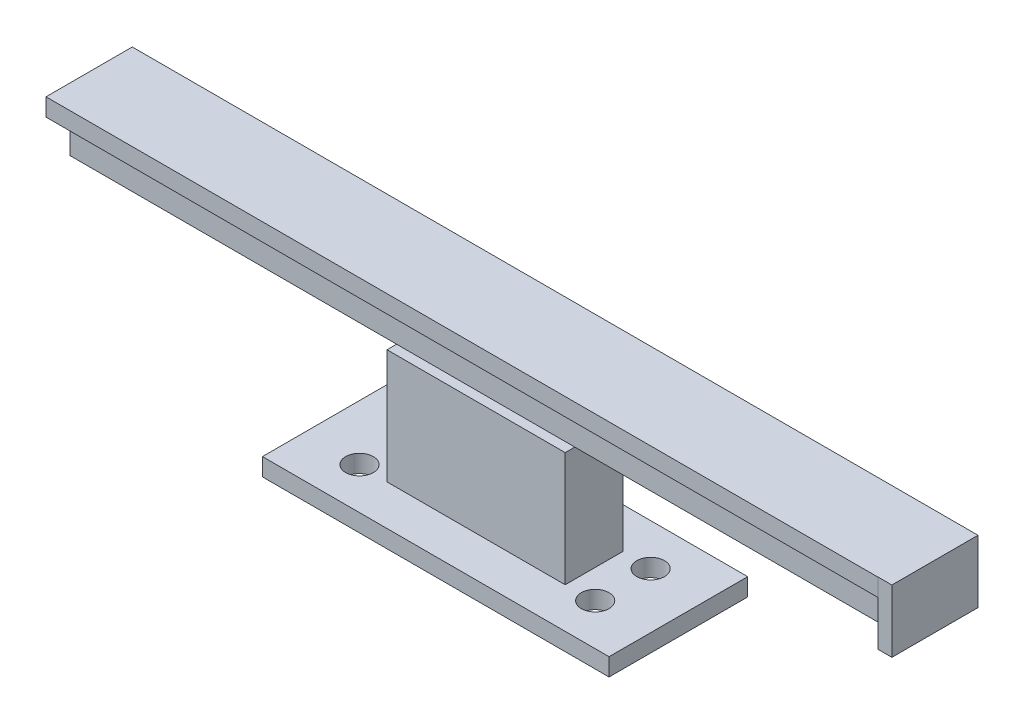
SolidWorks part; units mm, degrees
ref_plane "Front" through (0, 0, 0) normal (0, 0, 1) x (1, 0, 0)
ref_plane "Top" through (0, 0, 0) normal (0, 1, 0) x (1, 0, 0)
ref_plane "Right" through (0, 0, 0) normal (1, 0, 0) x (0, 0, -1)
sketch "Sketch1" plane through (0, 0, 0) normal (0, 1, 0) x (1, 0, 0)
  line L0 (0, 0) -> (0, -3.6978)
  line L1 (25, -12.5) -> (-25, -12.5)
  line L2 (25, -12.5) -> (25, 7.5)
  line L3 (25, 7.5) -> (-25, 7.5)
  line L4 (-25, -12.5) -> (-25, 7.5)
  circle A0 centre (17, -6.5) radius 2
  circle A1 centre (17, 1.5) radius 2
  circle A2 centre (-17, -6.5) radius 2
  circle A3 centre (-17, 1.5) radius 2
  point P0 (0, 0)
  dimension "D4" = 4
  dimension "D5" = 4
  dimension "D1" = 50
  dimension "D2" = 20
  dimension "D3" = 8
  dimension "D6" = 6
  dimension "D7" = 6
  dimension "D8" = 34
extrude "Boss-Extrude1" add sketch "Sketch1" along normal blind 2.54 contours L4 L1 L2 L3 A2 A1 A0 A3 region at (0, 0, 11.9615)
sketch "Sketch2" plane through (0, 2.54, 0) normal (0, 1, 0) x (1, 0, 0)
  line L1 (12.8489, -6.6773) -> (-12.8489, -6.6773)
  line L2 (12.8489, -6.6773) -> (12.8489, 1.6773)
  line L3 (12.8489, 1.6773) -> (-12.8489, 1.6773)
  line L4 (-12.8489, -6.6773) -> (-12.8489, 1.6773)
  line L5 (12.8489, -6.6773) -> (-12.8489, 1.6773) construction
  line L6 (12.8489, 1.6773) -> (-12.8489, -6.6773) construction
  point P0 (0, -2.5)
extrude "Boss-Extrude2" add sketch "Sketch2" along normal blind 16.51
sketch "Sketch3" plane through (0, 19.05, 0) normal (0, 1, 0) x (1, 0, 0)
  line L0 (-12.8489, -6.6773) -> (12.8489, -6.6773) construction
  line L1 (60, -5.294) -> (-60, -5.294)
  line L2 (60, -5.294) -> (60, 0.294)
  line L3 (60, 0.294) -> (-60, 0.294)
  line L4 (-60, -5.294) -> (-60, 0.294)
  line L5 (60, -5.294) -> (-60, 0.294) construction
  line L6 (60, 0.294) -> (-60, -5.294) construction
  line L7 (12.8489, -6.6773) -> (12.8489, 1.6773) construction
  point P0 (0, -2.5)
  point P5 (0, -2.5)
  dimension "D1" = 5.588
  dimension "D2" = 4.1773
  dimension "D3" = 0
  dimension "D4" = 12.8489
  dimension "D5" = 120
extrude "Boss-Extrude3" add sketch "Sketch3" along normal blind 6.51
sketch "Sketch4" plane through (0, 25.56, 0) normal (0, 1, 0) x (1, 0, 0)
  line L0 (60, 0.294) -> (-60, 0.294) construction
  line L1 (60, -8.723) -> (-60, -8.723)
  line L2 (60, -8.723) -> (60, 3.723)
  line L3 (60, 3.723) -> (-60, 3.723)
  line L4 (-60, -8.723) -> (-60, 3.723)
  line L5 (60, -8.723) -> (-60, 3.723) construction
  line L6 (60, 3.723) -> (-60, -8.723) construction
  point P0 (0, -2.5)
  point P1 (0, -2.5)
  point P6 (0, -2.5)
  point P9 (0, -2.5)
  dimension "D1" = 12.446
  dimension "D2" = 0
  dimension "D3" = 2.794
  dimension "D4" = 120
  dimension "D5" = 0
extrude "Boss-Extrude4" add sketch "Sketch4" along normal blind 2.54
sketch "Sketch6" plane through (60, 0, 0) normal (1, 0, 0) x (0, 0, -1)
  line L2 (3.723, 28.1) -> (-8.702, 28.1)
  line L3 (3.723, 28.1) -> (3.723, 19.0577)
  line L4 (3.723, 19.0577) -> (-8.702, 19.0577)
  line L5 (-8.702, 28.1) -> (-8.702, 19.0577)
extrude "Boss-Extrude6" add sketch "Sketch6" along normal blind 2
